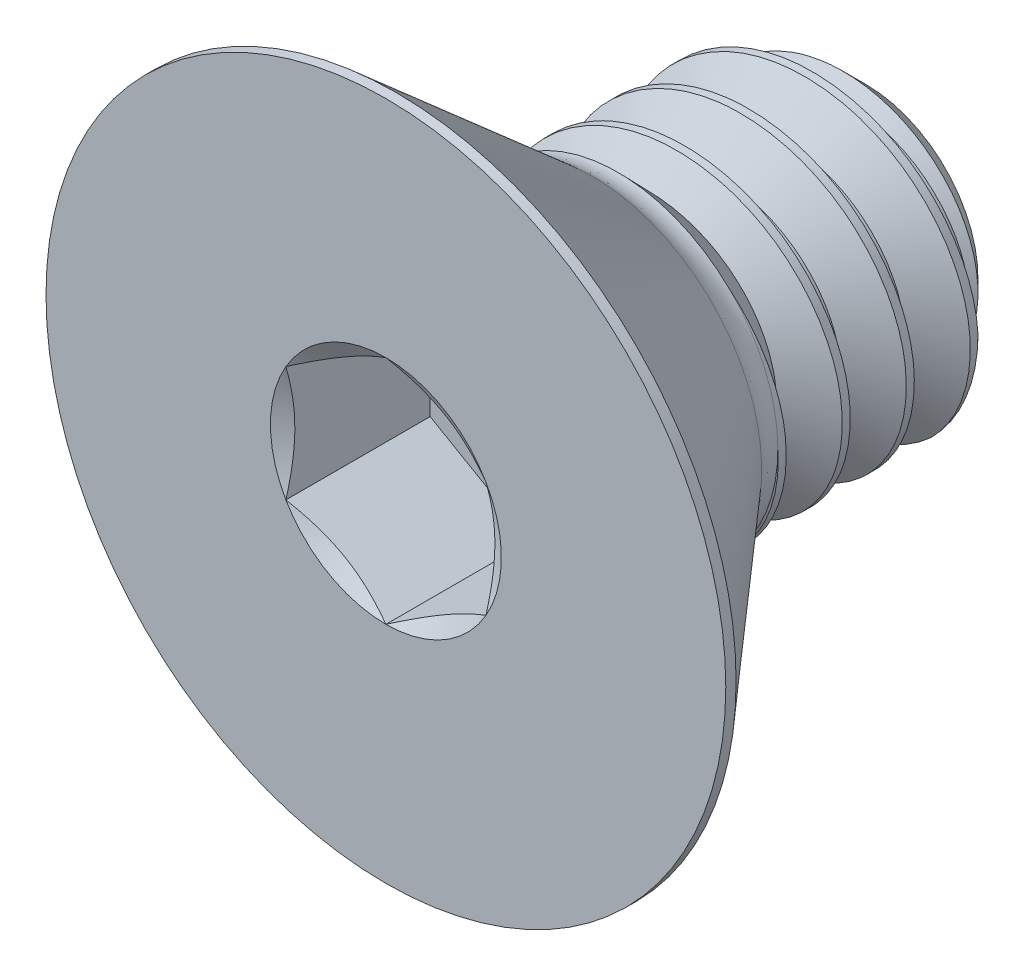
SolidWorks part; units mm, degrees
ref_plane "Front" through (0, 0, 0) normal (0, 0, 1) x (1, 0, 0)
ref_plane "Top" through (0, 0, 0) normal (0, 1, 0) x (1, 0, 0)
ref_plane "Right" through (0, 0, 0) normal (1, 0, 0) x (0, 0, -1)
sketch "Sketch1" plane through (0, 0, 0) normal (1, 0, 0) x (0, 0, -1)
  line L0 (0, 6.7437) -> (0.2045, 6.7437) construction
  line L1 (0.2045, 6.7437) -> (4.0894, 3.3666) construction
  line L2 (0, 3.175) -> (9.525, 3.175)
  line L3 (9.525, 3.175) -> (9.525, 0)
  line L4 (9.525, 0) -> (0, 0)
  line L5 (0, 0) -> (0, 6.7437) construction
  line L6 (0, 6.7437) -> (0, -6.7437) construction
  line L7 (9.525, 3.175) -> (9.525, -3.175) construction
  line L8 (0, -6.7437) -> (0.2045, -6.7437) construction
  line L9 (0.2045, -6.7437) -> (4.0894, -3.3666) construction
  line L11 (0, 3.175) -> (0, 0)
  line L12 (4.6018, 3.175) -> (4.6018, 0) construction
  line L13 (-15.875, 0) -> (-15.875, 3.175) construction
  arc A1 (4.0894, 3.3666) -> (4.6018, 3.175) centre (4.6018, 3.956) ccw construction
  dimension "D1" = 0.2045
  dimension "Min Thread" = 25.4
revolve "Revolve1" add sketch "Sketch1" angle 360 mid plane about L4
sketch "Sketch3" plane through (0, 0, -9.525) normal (0, 0, -1) x (-1, 0, 0)
  circle A0 centre (0, 0) radius 3.175
curve "Helix/Spiral1" pitch 1.27 height 9.525 radius 3.175 centre (0, 0, -9.525) axis (0, 0, 1) start towards (0, 1, 0)
sketch "Sketch2" plane through (0, 0, 0) normal (1, 0, 0) x (0, 0, -1)
  line L0 (9.525, 3.175) -> (10.6363, 3.175)
  line L1 (10.6363, 3.175) -> (10.16, 2.3501)
  line L2 (10.16, 2.3501) -> (10.0013, 2.3501)
  line L3 (10.0013, 2.3501) -> (9.525, 3.175)
  line L4 (9.7631, 2.7626) -> (10.3981, 2.7626) construction
  dimension "D1" = 60
  dimension "D2" = 0.1588
  dimension "D3" = 0.635
ref_plane "Plane2" through (0, 0, 15.875) normal (0, 0, 1) x (1, 0, 0)
chamfer "Chamfer1" distance 0.9525 angle 45 1 edges at (0, 3.175, -9.525)
sweep "Cut-Sweep1" cut profiles "Sketch2" path "Helix/Spiral1" align with end faces yes
sketch "Sketch7" plane through (0, 0, 0) normal (1, 0, 0) x (0, 0, -1)
  line L0 (0, 6.7437) -> (0.2045, 6.7437) construction
  line L1 (0.2045, 6.7437) -> (4.0894, 3.3666) construction
  line L2 (0, 6.7437) -> (0.2045, 6.7437)
  line L3 (0.2045, 6.7437) -> (4.0894, 3.3666)
  line L4 (4.6018, 3.175) -> (4.6018, 0) construction
  line L5 (4.6018, 3.175) -> (4.6018, 0)
  line L7 (0, 0) -> (0, 6.7437) construction
  line L8 (0, 0) -> (0, 6.7437)
  line L9 (0, 0) -> (4.6018, 0)
  line L10 (5.7417, 0) -> (-5.7417, 0) construction
  arc A0 (4.0894, 3.3666) -> (4.6018, 3.175) centre (4.6018, 3.956) ccw construction
  arc A1 (4.0894, 3.3666) -> (4.6018, 3.175) centre (4.6018, 3.956) ccw
revolve "Revolve2" add sketch "Sketch7" angle 360 mid plane about L9
ref_plane "Plane1" through (0, 0, -4.6018) normal (0, 0, 1) x (1, 0, 0)
sketch "Sketch8" plane through (0, 0, -4.6018) normal (0, 0, 1) x (1, 0, 0)
  circle A0 centre (0, 0) radius 3.175
extrude "Boss-Extrude1" add sketch "Sketch8" against normal through all draft 46
sketch "Sketch5" plane through (0, 0, 0) normal (0, 0, 1) x (1, 0, 0)
  line L0 (0, 0) -> (-2.2914, 0) construction
  line L1 (0, 0) -> (-2.7496, 1.5875) construction
  line L2 (0, 0) -> (-2.7496, -1.5875) construction
  line L6 (0, 2.2914) -> (0, 1.8898) construction
  line L7 (0, 1.8898) -> (0, 1.4883) construction
  line L9 (0, 2.2914) -> (-1.9844, 1.1457)
  line L10 (-1.9844, 1.1457) -> (-1.9844, -1.1457)
  line L11 (-1.9844, -1.1457) -> (0, -2.2914)
  line L12 (0, -2.2914) -> (1.9844, -1.1457)
  line L13 (1.9844, -1.1457) -> (1.9844, 1.1457)
  line L14 (1.9844, 1.1457) -> (0, 2.2914)
  circle A0 centre (0, 0) radius 2.2914 construction
  circle A1 centre (0, 0) radius 1.8898 construction
  circle A2 centre (0, 0) radius 1.4883 construction
  circle A3 centre (0, 0) radius 1.9844 construction
  dimension "D3" = 2.9766
  dimension "D4" = 30
  dimension "D5" = 30
  dimension "Hex" = 3.9688
extrude "Cut-Extrude2" cut sketch "Sketch5" against normal blind 2.8626
sketch "Sketch6" plane through (0, 0, 0) normal (0, 0, 1) x (1, 0, 0)
  circle A0 centre (0, 0) radius 2.2914
extrude "Cut-Extrude3" cut sketch "Sketch6" against normal blind 2.8626 draft 60
sketch "Sketch9" [suppressed] plane through (0, 0, -3.6076) normal (0, 0, 1) x (1, 0, 0)
  circle A1 centre (0, 0) radius 2.413
  circle A2 centre (0, 0) radius 2.413
  point P0 (0, 2.413)
  dimension "D1" = 0
extrude "Boss-Extrude2" [suppressed] add sketch "Sketch9" against normal up to surface (15.4424 mm away) up to plane "Plane2"
sketch "Sketch10" plane through (0, 0, 0) normal (1, 0, 0) x (0, 0, -1)
  line L0 (9.525, 3.175) -> (9.525, -3.175) construction
  point P0 (7.62, -3.175)
  dimension "D1" = 1.905
equation "\"D3@Helix/Spiral1\" = \"Lg@Sketch1\""
equation "\"D2@Sketch2\" = \"D4@Helix/Spiral1\" * .125"
equation "\"D3@Sketch2\" = \"D4@Helix/Spiral1\" * .5"
equation "\"D1@Chamfer1\" = \"D4@Helix/Spiral1\" * .75"
equation "\"D1@Cut-Extrude2\" = \"Head Ht@Sketch1\" * .7"
equation "\"D1@Sketch1\" = \"Head Ht@Sketch1\" * .05"
equation "\"D1@Sketch10\" = \"D4@Helix/Spiral1\" * 1.5"
equation "\"D1@Cut-Extrude3\" = \"D1@Cut-Extrude2\""
equation "\"D3@Sketch5\" = \"Hex@Sketch5\" * .75"
